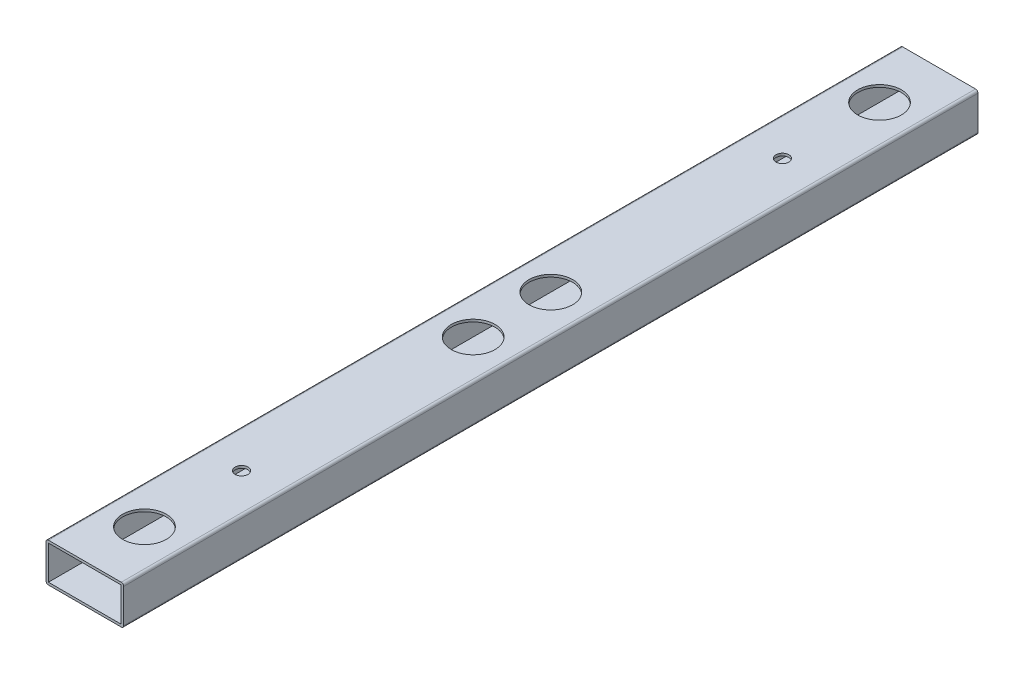
SolidWorks part; units mm, degrees
ref_plane "Front Plane" through (0, 0, 0) normal (0, 0, 1) x (1, 0, 0)
ref_plane "Top Plane" through (0, 0, 0) normal (0, 1, 0) x (1, 0, 0)
ref_plane "Right Plane" through (0, 0, 0) normal (1, 0, 0) x (0, 0, -1)
sketch "Sketch1" plane through (0, 0, 0) normal (0, 0, 1) x (1, 0, 0)
  line L0 (-23.8125, 11.1125) -> (23.8125, 11.1125)
  line L1 (-23.8125, -12.7) -> (23.8125, -12.7)
  line L2 (-25.4, -11.1125) -> (-25.4, 11.1125)
  line L3 (-23.8125, 12.7) -> (23.8125, 12.7)
  line L4 (25.4, -11.1125) -> (25.4, 11.1125)
  line L5 (-25.4, -12.7) -> (25.4, 12.7) construction
  line L6 (-25.4, 12.7) -> (25.4, -12.7) construction
  line L7 (23.8125, -11.1125) -> (23.8125, 11.1125)
  line L8 (-23.8125, -11.1125) -> (23.8125, -11.1125)
  line L9 (-23.8125, -11.1125) -> (-23.8125, 11.1125)
  line L10 (-25.4, -12.7) -> (25.4, -12.7) construction
  line L11 (-25.4, -12.7) -> (-25.4, 12.7) construction
  line L12 (25.4, -12.7) -> (25.4, 12.7) construction
  line L13 (-25.4, 12.7) -> (25.4, 12.7) construction
  arc A0 (-23.8125, -12.7) -> (-25.4, -11.1125) centre (-23.8125, -11.1125) cw
  arc A1 (23.8125, -12.7) -> (25.4, -11.1125) centre (23.8125, -11.1125) ccw
  arc A2 (23.8125, 12.7) -> (25.4, 11.1125) centre (23.8125, 11.1125) cw
  arc A3 (-25.4, 11.1125) -> (-23.8125, 12.7) centre (-23.8125, 11.1125) cw
  point P0 (0, 0)
  dimension "D4" = 1.5875
  dimension "D1" = 25.4
  dimension "D2" = 50.8
  dimension "D3" = 1.5875
extrude "Boss-Extrude1" add sketch "Sketch1" along normal blind 558.8
sketch "Sketch2" plane through (0, 12.7, 0) normal (0, 1, 0) x (1, 0, 0)
  line L2 (0, -519.8) -> (0, -304.8) construction
  line L3 (0, -304.8) -> (0, -254) construction
  line L4 (0, -254) -> (0, -39) construction
  line L5 (0, -519.8) -> (0, -558.8) construction
  line L6 (23.8125, -558.8) -> (-23.8125, -558.8) construction
  line L7 (0, -39) -> (0, 0) construction
  line L8 (23.8125, 0) -> (-23.8125, 0) construction
  circle A8 centre (0, -519.8) radius 14.2875
  circle A9 centre (0, -304.8) radius 14.2875
  circle A10 centre (0, -254) radius 14.2875
  circle A11 centre (0, -39) radius 14.2875
  point P7 (0, -212.7741)
  point P9 (0, -80.402)
  point P16 (0, -261.3622)
  dimension "D1" = 28.575
  dimension "D4" = 50.8
  dimension "D2" = 28.575
  dimension "D3" = 215
extrude "Cut-Extrude1" cut sketch "Sketch2" against normal up to next and the other way through all
sketch "Sketch3" plane through (0, -12.7, 0) normal (0, -1, 0) x (1, 0, 0)
  circle A0 centre (0, 39) radius 12.7
  circle A1 centre (0, 254) radius 12.7
  circle A2 centre (0, 304.8) radius 12.7
  circle A3 centre (0, 519.8) radius 12.7
  circle A4 centre (0, 519.8) radius 14.2875 construction
  circle A6 centre (0, 304.8) radius 14.2875 construction
  circle A7 centre (0, 254) radius 14.2875 construction
  circle A8 centre (0, 39) radius 14.2875 construction
  dimension "D1" = 25.4
  dimension "D2" = 25.4
extrude "Cut-Extrude2" cut sketch "Sketch3" against normal up to next and the other way through all
sketch "Sketch4" plane through (0, 12.7, 0) normal (0, 1, 0) x (1, 0, 0)
  line L0 (0, -39) -> (0, -254) construction
  line L1 (0, -304.8) -> (0, -519.8) construction
  circle A0 centre (0, -456.3) radius 4.2044
  circle A1 centre (0, -102.5) radius 4.2044
  dimension "D1" = 63.5
  dimension "D2" = 63.5
extrude "Cut-Extrude3" cut sketch "Sketch4" against normal up to next and the other way through all
sketch "Sketch5" plane through (0, -12.7, 0) normal (0, -1, 0) x (1, 0, 0)
  line L0 (0, 39) -> (0, 254) construction
  line L1 (0, 304.8) -> (0, 519.8) construction
  circle A0 centre (0, 102.5) radius 7.9375
  circle A1 centre (0, 456.3) radius 7.9375
  circle A2 centre (0, 102.5) radius 4.2044 construction
  circle A3 centre (0, 456.3) radius 4.2044 construction
  point P14 (0, 0)
  point P15 (0, 0)
  dimension "D1" = 15.875
extrude "Cut-Extrude4" cut sketch "Sketch5" against normal up to next and the other way through all
